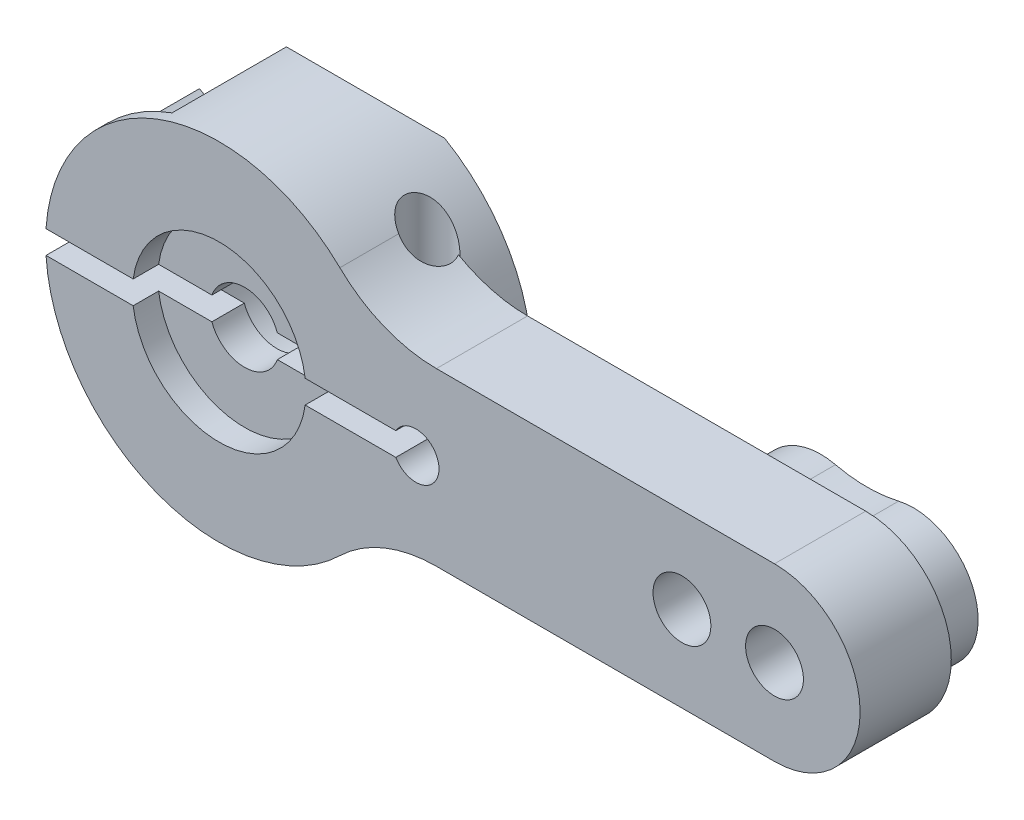
SolidWorks part; units mm, degrees
ref_plane "Спереди (XY)" through (0, 0, 0) normal (0, 0, 1) x (1, 0, 0)
ref_plane "Сверху (XZ)" through (0, 0, 0) normal (0, 1, 0) x (1, 0, 0)
ref_plane "Справа (ZY)" through (0, 0, 0) normal (1, 0, 0) x (0, 0, -1)
sketch "Эскиз1" plane through (0, 0, 0) normal (0, 0, 1) x (1, 0, 0)
  line L0 (24, 3.7) -> (6.5238, 3.7)
  line L1 (24, -3.7) -> (6.5238, -3.7)
  line L2 (24, 0) -> (20, 0) construction
  line L3 (1.4142, 0.5) -> (7.634, 0.5)
  line L4 (0, 0) -> (12.6344, 0) construction
  line L5 (1.4142, -0.5) -> (7.634, -0.5)
  line L6 (-1.4142, 0.5) -> (-7.4833, 0.5)
  line L7 (-1.4142, -0.5) -> (-7.4833, -0.5)
  circle A0 centre (0, 0) radius 1.5
  circle A1 centre (0, 0) radius 2.75
  circle A2 centre (0, 0) radius 7.5
  arc A3 (24, -3.7) -> (24, 3.7) centre (24, 0) ccw
  circle A4 centre (24, 0) radius 1.25
  arc A5 (23.3636, -2.7267) -> (23.3636, 2.7267) centre (24, 0) ccw
  circle A6 centre (20, 0) radius 1.25
  arc A7 (20.6364, 2.7267) -> (20.6364, -2.7267) centre (20, 0) ccw
  circle A8 centre (0, 0) radius 3.75
  arc A9 (20.6364, -2.7267) -> (23.3636, -2.7267) centre (22, -8.5697) cw
  arc A10 (20.6364, 2.7267) -> (23.3636, 2.7267) centre (22, 8.5697) ccw
  circle A11 centre (8.5, 0) radius 1
  dimension "D1" = 15
  dimension "D2" = 3
  dimension "D3" = 5.5
  dimension "D4" = 7.5
  dimension "D6" = 20
  dimension "D7" = 24
  dimension "D8" = 2.5
  dimension "D9" = 5.6
  dimension "D10" = 6
  dimension "D12" = 2
  dimension "D13" = 8.5
  dimension "D5" = 7.4
  dimension "D11" = 1
extrude "Бобышка-Вытянуть1" add sketch "Эскиз1" along normal blind 6 contours A11 L5 A2 L1 A3 L0 L3 A7 A10 A5 A9 | A10 A7 A9 A5 A6 A4 | A8 L3 A2 L6 | L3 A8 L6 A1 | L3 A1 L6 A0 | A8 L7 A2 L5 | L7 A8 L5 A1 | L7 A1 L5 A0 region at (14.9944, 0, 0) region at (0, 3.9217, 0) region at (0, -3.9217, 0) region at (0, 3.6689, 0) region at (0, 1.5952, 0) region at (-3.2103, -0.5811, 0) region at (0, -1.5952, 0) region at (22, 0, 0)
extrude "Вырез-Вытянуть1" cut sketch "Эскиз1<3>" along normal blind 2.06 contours A11 L5 A2 L1 A3 L0 L3 A7 A10 A5 A9 region at (14.9944, 0, 0)
sketch "Эскиз1<3>" plane through (0, 0, 0) normal (0, 0, 1) x (1, 0, 0) same geometry as "Эскиз1"
extrude "Вырез-Вытянуть2" cut sketch "Эскиз1<4>" along normal blind 3.5 contours A1
sketch "Эскиз1<4>" plane through (0, 0, 0) normal (0, 0, 1) x (1, 0, 0) same geometry as "Эскиз1"
extrude "Вырез-Вытянуть3" cut sketch "Эскиз1<5>" against normal blind 1.1 from surface contours A8 starting at face at (5.3778, 0, 6)
sketch "Эскиз1<5>" plane through (0, 0, 0) normal (0, 0, 1) x (1, 0, 0) same geometry as "Эскиз1"
fillet "Скругление1" radius 6 2 edges at (6.5238, -3.7, 4.03) (6.5238, 3.7, 4.03)
sketch "Эскиз2" plane through (0, 0, 0) normal (0, 0, 1) x (1, 0, 0)
  line L0 (0, 0) -> (-5.099, 5.5) construction
  line L1 (0, 0) -> (10.198, -11) construction
  line L2 (-2.7042, 0.5) -> (-7.4833, 0.5) construction
  circle A0 centre (5.099, -5.5) radius 3
  circle A1 centre (-5.099, 5.5) radius 3
  circle A2 centre (0, 0) radius 7.5 construction
  point P7 (-5.099, 2.5)
  dimension "D1" = 6
  dimension "D3" = 15
  dimension "D2" = 2
extrude "Вырез-Вытянуть4" cut sketch "Эскиз2" along normal blind 5.5
sketch "Эскиз3" plane through (0, 0, 0) normal (0, 1, 0) x (1, 0, 0)
  line L0 (0, 0) -> (0, -19.0596) construction
  line L1 (-7.4833, -6) -> (5.2163, -6) construction
  circle A0 centre (5.5, -2.5) radius 1
  circle A1 centre (-5.5, -2.5) radius 1
  dimension "D3" = 2
  dimension "D1" = 3.5
  dimension "D2" = 5.5
extrude "Вырез-Вытянуть5" cut sketch "Эскиз3" against normal through all both and the other way through all
sketch "Эскиз4" plane through (0, 0, 0) normal (1, 0, 0) x (0, 0, -1)
  line L0 (0, -6.5) -> (-1, -7.5)
  line L1 (-1, -7.5) -> (0, -7.5)
  line L2 (0, -7.5) -> (0, -6.5)
  line L3 (0, -7.5) -> (0, -0.5) construction
  line L4 (-6, -7.5) -> (0, -7.5) construction
  line L5 (0, 0) -> (12.563, 0) construction
  line L6 (0, 7.5) -> (0, 6.5)
  line L7 (-1, 7.5) -> (0, 7.5)
  line L8 (0, 6.5) -> (-1, 7.5)
  dimension "D1" = 1
extrude "Вырез-Вытянуть6" cut sketch "Эскиз4" against normal through all both and the other way through all
